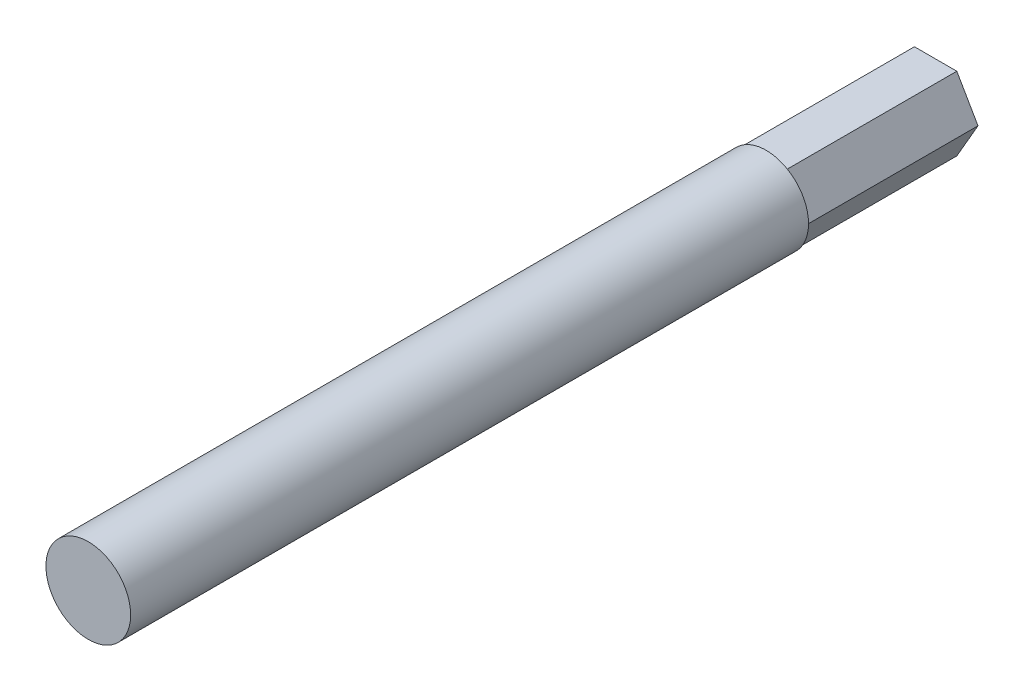
SolidWorks part; units mm, degrees
ref_plane "Front Plane" through (0, 0, 0) normal (0, 0, 1) x (1, 0, 0)
ref_plane "Top Plane" through (0, 0, 0) normal (0, 1, 0) x (1, 0, 0)
ref_plane "Right Plane" through (0, 0, 0) normal (1, 0, 0) x (0, 0, -1)
sketch "Sketch1" plane through (0, 0, 0) normal (0, 0, 1) x (1, 0, 0)
  circle A0 centre (0, 0) radius 6.35
  dimension "D1" = 12.7
extrude "Boss-Extrude1" add sketch "Sketch1" along normal blind 63.5 and the other way blind 63.5
sketch "Sketch2" plane through (0, 0, -63.5) normal (0, 0, -1) x (-1, 0, 0)
  line L0 (0, 0) -> (0, 6.8395) construction
  line L1 (3.175, 5.4993) -> (-3.175, 5.4993)
  line L2 (-3.175, 5.4993) -> (-6.35, 0)
  line L3 (-6.35, 0) -> (-3.175, -5.4993)
  line L4 (-3.175, -5.4993) -> (3.175, -5.4993)
  line L5 (3.175, -5.4993) -> (6.35, 0)
  line L6 (6.35, 0) -> (3.175, 5.4993)
  circle A0 centre (0, 0) radius 6.35 construction
  circle A2 centre (0, 0) radius 6.35
  circle A3 centre (0, 0) radius 6.35
  circle M9 centre (0, 0) radius 6.35
  dimension "D1" = 0
extrude "Cut-Extrude1" cut sketch "Sketch2" against normal blind 25.4 contours L1 M9 | L6 M9 | L5 M9 | L4 M9 | L3 M9 | L2 M9 region at (-5.059, 2.9208, -63.5) region at (0, 5.8416, -63.5) region at (5.059, 2.9208, -63.5) region at (-5.059, -2.9208, -63.5) region at (5.059, -2.9208, -63.5) region at (0, -5.8416, -63.5)
